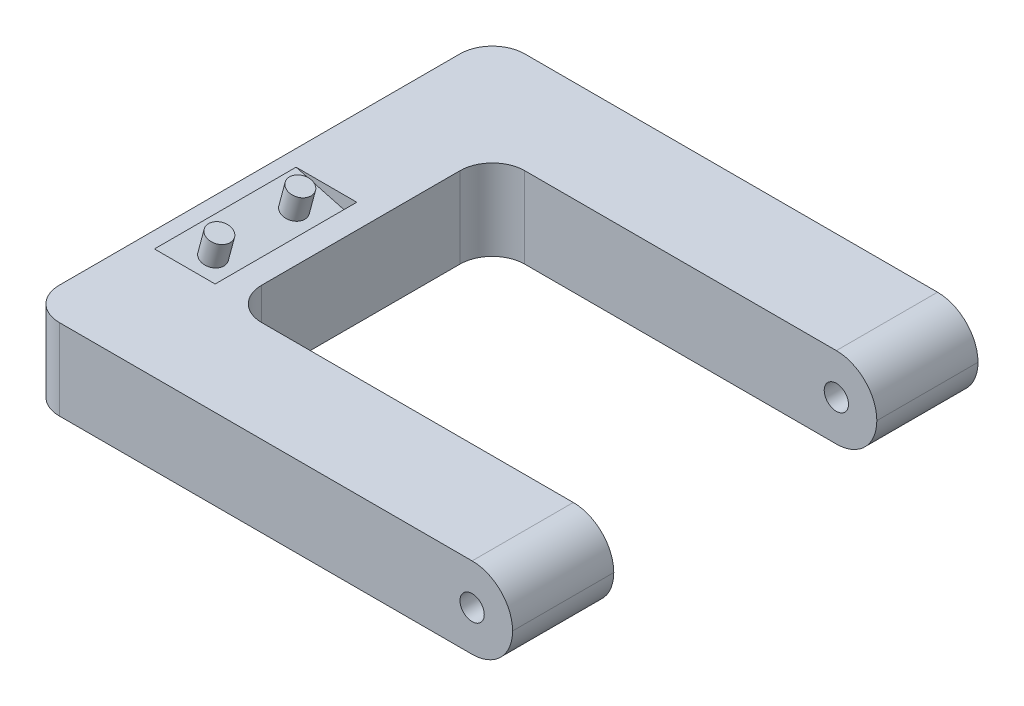
SolidWorks part; units mm, degrees
ref_plane "Front" through (0, 0, 0) normal (0, 0, 1) x (1, 0, 0)
ref_plane "Top" through (0, 0, 0) normal (0, 1, 0) x (1, 0, 0)
ref_plane "Right" through (0, 0, 0) normal (1, 0, 0) x (0, 0, -1)
sketch "Sketch1" plane through (0, 0, 0) normal (0, 1, 0) x (1, 0, 0)
  line L0 (47.5, 57.5) -> (47.5, 32.5)
  line L1 (47.5, 32.5) -> (-47.5, 32.5)
  line L2 (-47.5, 32.5) -> (-47.5, -32.5)
  line L3 (-47.5, -32.5) -> (47.5, -32.5)
  line L4 (47.5, -32.5) -> (47.5, -57.5)
  line L5 (47.5, -57.5) -> (-72.5, -57.5)
  line L6 (-72.5, -57.5) -> (-72.5, 57.5)
  line L7 (-72.5, 57.5) -> (47.5, 57.5)
  point P2 (-47.5, 0)
  point P9 (0, -32.5)
  dimension "D1" = 25
  dimension "D2" = 25
  dimension "D3" = 120
  dimension "D4" = 65
extrude "Boss-Extrude1" add sketch "Sketch1" along normal mid plane 20
fillet "Fillet1" radius 10 4 edges at (47.5, 10, -45) (47.5, -10, -45) (47.5, -10, 45) (47.5, 10, 45)
fillet "Fillet2" radius 8 4 edges at (-72.5, 0, -57.5) (-72.5, 0, 57.5) (-47.5, 0, -32.5) (-47.5, 0, 32.5)
hole_wizard "Ø6.0mm Dowel Hole1" positions "Sketch2" profile "Sketch3" hole size "Ø6.0" standard "ANSI Metric" end condition through all
sketch "Sketch2" plane through (0, 0, 57.5) normal (0, 0, 1) x (1, 0, 0)
  point P0 (37.5, 0)
sketch "Sketch3" plane through (37.5, 0, 57.5) normal (1, 0, 0) x (0, -1, 0)
  line L0 (0, 0) -> (0, 115)
  line L1 (0, 115) -> (3, 115)
  line L2 (3, 115) -> (3, 0)
  line L5 (3, 0) -> (0, 0)
  line L11 (0, -6.35) -> (0, 107.95) construction
  dimension "Thru Hole Dia." = 6
  dimension "Thru Hole Depth" = 115
ref_plane "Plane1" through (0, 0, 12.5) normal (0, 0, 1) x (1, 0, 0)
sketch "Sketch4" plane through (0, 0, 12.5) normal (0, 0, 1) x (1, 0, 0)
  line L0 (-68.5, 10) -> (-53.5, 5.9808)
  line L1 (-53.5, 5.9808) -> (-53.5, 10)
  line L2 (-64.5, 10) -> (37.5, 10) construction
  line L3 (-53.5, 10) -> (-68.5, 10)
  line L4 (-64.5, 10) -> (-72.5, 10) construction
  point P3 (-68.5, 10)
  dimension "D1" = 15
  dimension "D2" = 15
extrude "Cut-Extrude1" cut sketch "Sketch4" against normal mid plane 35
sketch "Sketch5" plane through (-2.0886, -7.7949, 0) normal (0.2588, 0.9659, 0) x (0.9659, -0.2588, 0)
  line L2 (-54.2652, 5) -> (-68.7541, 5) construction
  line L3 (-61.5097, -2.5) -> (-61.5097, -22.5) construction
  line L4 (-68.7541, 5) -> (-68.7541, -30) construction
  circle A0 centre (-61.5097, -2.5) radius 2.75
  circle A1 centre (-61.5097, -22.5) radius 2.75
  point P4 (-61.5097, -12.5)
  point P9 (-61.5097, 5)
  point P10 (-68.7541, -12.5)
  dimension "D1" = 5.5
  dimension "D2" = 5.5
  dimension "D3" = 20
extrude "Boss-Extrude2" add sketch "Sketch5" along normal blind 6
